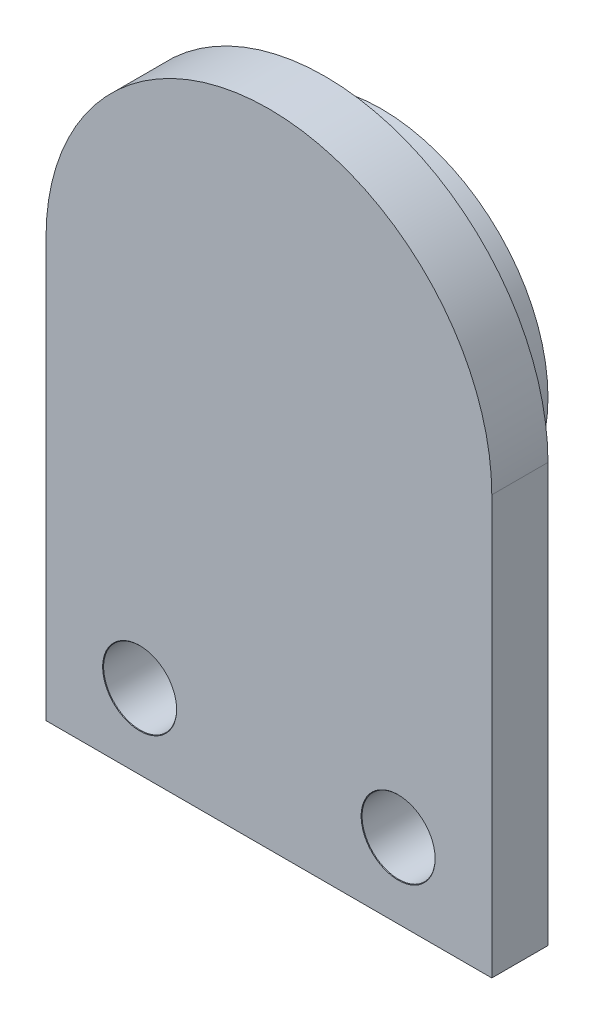
SolidWorks part; units mm, degrees
ref_plane "Front Plane" through (0, 0, 0) normal (0, 0, 1) x (1, 0, 0)
ref_plane "Top Plane" through (0, 0, 0) normal (0, 1, 0) x (1, 0, 0)
ref_plane "Right Plane" through (0, 0, 0) normal (1, 0, 0) x (0, 0, -1)
sketch "Sketch1" plane through (0, 0, 0) normal (0, 0, 1) x (1, 0, 0)
  line L0 (-11.9, 0) -> (-11.9, -22.34)
  line L1 (-11.9, -22.34) -> (11.9, -22.34)
  line L2 (11.9, -22.34) -> (11.9, 0)
  arc A0 (11.9, 0) -> (-11.9, 0) centre (0, 0) ccw
  dimension "D1" = 22.34
  dimension "D2" = 23.8
extrude "Boss-Extrude1" add sketch "Sketch1" along normal blind 3
sketch "Sketch2" plane through (0, 0, 0) normal (0, 0, -1) x (-1, 0, 0)
  circle A0 centre (0, 0) radius 8.9
  dimension "D1" = 17.8
extrude "Boss-Extrude2" add sketch "Sketch2" along normal blind 3
sketch "Sketch3" plane through (0, 0, -3) normal (0, 0, -1) x (-1, 0, 0)
  circle A0 centre (0, 0) radius 2
  dimension "D1" = 4
extrude "Boss-Extrude3" add sketch "Sketch3" along normal blind 3
hole_wizard "M3.5 Clearance Hole1" positions "3DSketch1" profile "Sketch5" hole size "M3.5" standard "ANSI Metric" end condition through all
sketch3d "3DSketch1"
  line L0 (-11.9, -22.34, 3) -> (11.9, -22.34, 3) construction
  line L1 (-11.9, 0, 3) -> (-11.9, -22.34, 3) construction
  line L2 (11.9, -22.34, 3) -> (11.9, 0, 3) construction
  point P0 (-6.9, -18.34, 3)
  point P2 (6.9, -18.34, 3)
  point P12 (0, 0, 0)
  dimension "D1" = 4
  dimension "D2" = 5
  dimension "D3" = 5
sketch "Sketch5" plane through (-6.9, -18.34, 3) normal (1, 0, 0) x (0, -1, 0)
  line L0 (0, 0) -> (0, 9)
  line L1 (0, 9) -> (1.95, 9)
  line L2 (1.95, 9) -> (1.95, 0.025)
  line L3 (1.95, 0.025) -> (1.975, 0)
  line L5 (1.975, 0) -> (0, 0)
  line L6 (-1.95, 0.025) -> (-1.975, 0) construction
  line L11 (0, -6.35) -> (0, 107.95) construction
  dimension "Thru Hole Dia." = 3.9
  dimension "Thru Hole Depth" = 9
  dimension "Near C'Sink Dia." = 3.95
  dimension "Near C'Sink Angle" = 90
